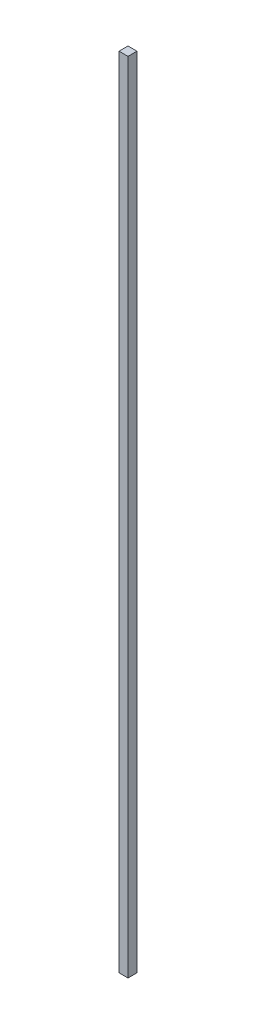
SolidWorks part; units mm, degrees
ref_plane "Front Plane" through (0, 0, 0) normal (0, 0, 1) x (1, 0, 0)
ref_plane "Top Plane" through (0, 0, 0) normal (0, 1, 0) x (1, 0, 0)
ref_plane "Right Plane" through (0, 0, 0) normal (1, 0, 0) x (0, 0, -1)
sketch "Sketch1" plane through (0, 0, 0) normal (0, 1, 0) x (1, 0, 0)
  line L1 (0, 0) -> (25.4, 0)
  line L2 (0, 0) -> (0, 25.4)
  line L3 (0, 25.4) -> (25.4, 25.4)
  line L4 (25.4, 0) -> (25.4, 25.4)
  dimension "D1" = 25.4
  dimension "D2" = 25.4
extrude "Boss-Extrude1" add sketch "Sketch1" along normal blind 2260.6
